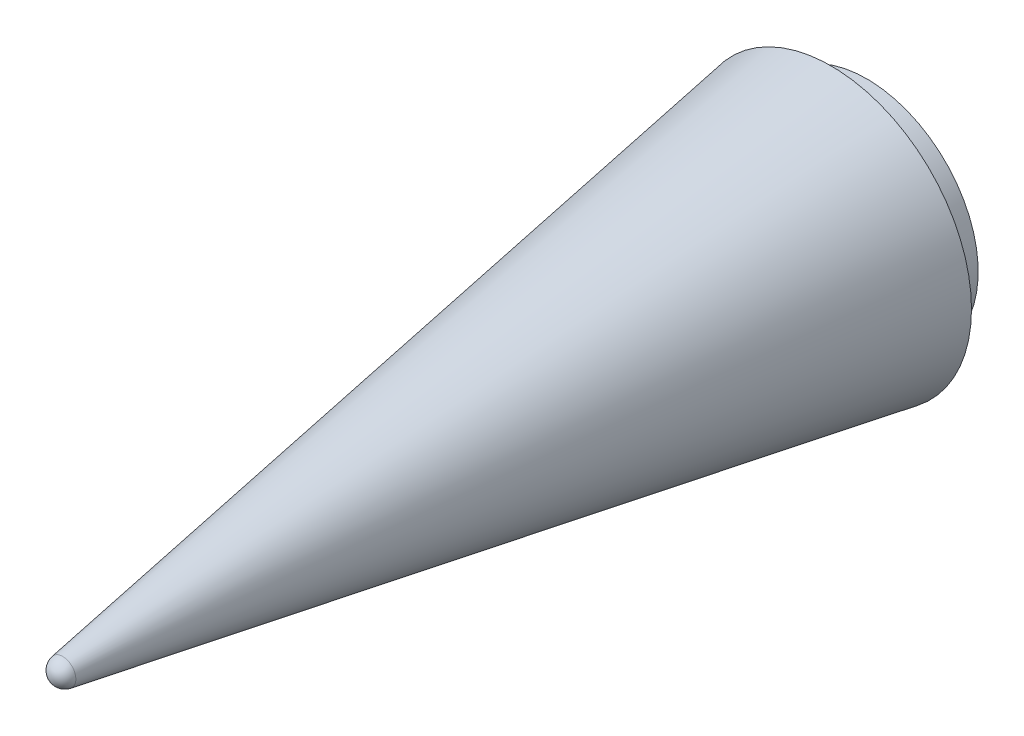
SolidWorks part; units mm, degrees
material "6061 Alloy"
ref_plane "Front Plane" through (0, 0, 0) normal (0, 0, 1) x (1, 0, 0)
ref_plane "Top Plane" through (0, 0, 0) normal (0, 1, 0) x (1, 0, 0)
ref_plane "Right Plane" through (0, 0, 0) normal (1, 0, 0) x (0, 0, -1)
sketch "Sketch3" plane through (0, 0, 0) normal (1, 0, 0) x (0, 0, -1)
  line L0 (0, 0) -> (-45.75, 0)
  line L1 (0, 0) -> (0, 6.25)
  line L2 (0, 6.25) -> (-2, 6.25)
  line L3 (-2, 6.25) -> (-2, 7.875)
  line L4 (-2, 7.875) -> (-45.1224, 0.7399)
  arc A0 (-45.75, 0) -> (-45.1224, 0.7399) centre (-45, 0) cw
  point P8 (0, 0)
  dimension "D2" = 6.25
  dimension "D5" = 0.75
  dimension "D1" = 45.75
  dimension "D3" = 7.875
  dimension "D4" = 2
revolve "Revolve1" add sketch "Sketch3" angle 360 about L0
sketch "Sketch4" plane through (0, 0, 0) normal (0, 0, -1) x (-1, 0, 0)
  point P0 (0, 0)
  point P1 (0, 0)
sketch "Sketch7" plane through (0, 0, 0) normal (0, 0, -1) x (-1, 0, 0)
  point P0 (0, 0)
hole_wizard "1/4 (0.25) Diameter Hole1" positions "Sketch7" profile "Sketch6" hole size "1/4" standard "ANSI Inch"
sketch "Sketch6" plane through (0, 0, 0) normal (1, 0, 0) x (0, 1, 0)
  line L0 (0, 0) -> (0, 27.3077)
  line L1 (0, 27.3077) -> (3.175, 25.4)
  line L2 (3.175, 25.4) -> (3.175, 0)
  line L5 (3.175, 0) -> (0, 0)
  line L10 (0, 27.3077) -> (-3.175, 25.4) construction
  line L11 (0, -6.35) -> (0, 107.95) construction
  dimension "Hole Dia." = 6.35
  dimension "Hole Depth" = 25.4
  dimension "Drill Angle" = 118
chamfer "Chamfer1" distance 0.635 angle 45 1 edges at (-3.175, 0, 0)
thread "Thread1" pitch 1.27 method cut profile "Thread Profile1" start angle 0, offset 3.175, length 25.4, pitch 1.27, diameter 6.35
ref_plane "Plane1" through (3.175, 0, -2.54) normal (0, 1, 0) x (-1, 0, 0)
sketch "Thread Profile1" plane through (3.175, 0, -2.54) normal (0, 1, 0) x (-1, 0, 0)
  line L0 (0, 0) -> (0, 1.27) construction
  line L11 (0, 0) -> (0, 1.1112)
  line L12 (0, 1.1112) -> (-0.6874, 0.7144)
  line L13 (-0.6874, 0.7144) -> (-0.6874, 0.3969)
  line L15 (-0.6874, 0.3969) -> (0, 0)
  line L17 (-0.6874, 0.5556) -> (0, 0.5556) construction
  point P2 (0, 0)
  dimension "Pitch" = 1.27
  dimension "Profile_Angle" = 60
  dimension "Profile_Land" = 0.3175
  dimension "Profile_Height" = 0.6874
